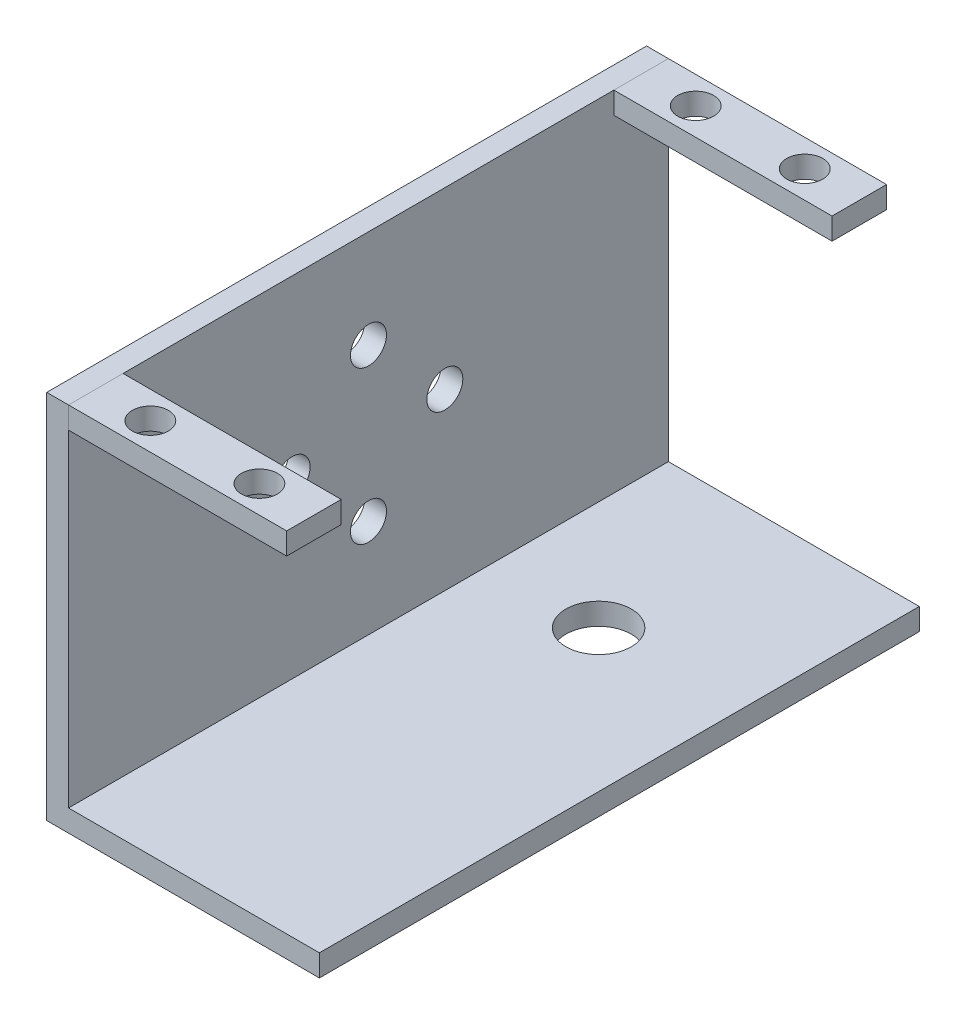
SolidWorks part; units mm, degrees
ref_plane "前视基准面" through (0, 0, 0) normal (0, 0, 1) x (1, 0, 0)
ref_plane "上视基准面" through (0, 0, 0) normal (0, 1, 0) x (1, 0, 0)
ref_plane "右视基准面" through (0, 0, 0) normal (1, 0, 0) x (0, 0, -1)
sketch "草图1" plane through (0, 0, 0) normal (0, 1, 0) x (1, 0, 0)
  line L1 (-12.5, -27.5) -> (12.5, -27.5)
  line L2 (-12.5, -27.5) -> (-12.5, 27.5)
  line L3 (-12.5, 27.5) -> (12.5, 27.5)
  line L4 (12.5, -27.5) -> (12.5, 27.5)
  line L5 (-12.5, -27.5) -> (12.5, 27.5) construction
  line L6 (-12.5, 27.5) -> (12.5, -27.5) construction
  point P1 (0, 0)
  dimension "D1" = 55
  dimension "D2" = 25
extrude "凸台-拉伸1" add sketch "草图1" along normal blind 2
sketch "草图3" plane through (0, 2, 0) normal (0, 1, 0) x (1, 0, 0)
  line L0 (-12.5, -27.5) -> (12.5, -27.5) construction
  line L1 (-12.5, 27.5) -> (-10.5, 27.5)
  line L2 (-12.5, 27.5) -> (-12.5, -27.5)
  line L3 (-12.5, -27.5) -> (-10.5, -27.5)
  line L4 (-10.5, 27.5) -> (-10.5, -27.5)
  dimension "D1" = 2
extrude "凸台-拉伸2" add sketch "草图3" along normal blind 32
sketch "草图4" plane through (-10.5, 0, 0) normal (1, 0, 0) x (0, 0, -1)
  line L0 (0, 34) -> (0, 2) construction
  line L1 (-27.5, 34) -> (27.5, 34) construction
  line L2 (-27.5, 2) -> (27.5, 2) construction
  line L3 (-22.5, 32) -> (22.5, 32) construction
  line L4 (22.5, 34) -> (27.5, 34)
  line L5 (-22.5, 32) -> (-27.5, 32)
  line L6 (-22.5, 32) -> (-22.5, 34)
  line L7 (-22.5, 34) -> (-27.5, 34)
  line L8 (-27.5, 32) -> (-27.5, 34)
  line L9 (27.5, 32) -> (27.5, 34)
  line L10 (22.5, 32) -> (27.5, 32)
  line L11 (22.5, 32) -> (22.5, 34)
  line L12 (-27.5, 2) -> (27.5, 2) construction
  dimension "D1" = 45
  dimension "D2" = 5
  dimension "D3" = 2
  dimension "D4" = 30
extrude "凸台-拉伸3" add sketch "草图4" along normal blind 20 separate body
sketch "草图5" plane through (0, 34, 0) normal (0, 1, 0) x (1, 0, 0)
  line L0 (-10.5, -25) -> (9.5, -25) construction
  line L1 (-10.5, -22.5) -> (-10.5, -27.5) construction
  line L2 (9.5, -22.5) -> (9.5, -27.5) construction
  line L3 (-12.5, 0) -> (-10.5, 0) construction
  line L4 (-12.5, 27.5) -> (-12.5, -27.5) construction
  line L5 (-10.5, -27.5) -> (-10.5, 27.5) construction
  circle A0 centre (-5.5, -25) radius 1.65
  circle A1 centre (4.5, -25) radius 1.65
  circle A2 centre (4.5, 25) radius 1.65
  circle A3 centre (-5.5, 25) radius 1.65
  dimension "D1" = 3.3
  dimension "D2" = 3.3
  dimension "D3" = 10
  dimension "D4" = 5
extrude "切除-拉伸2" cut sketch "草图5" against normal up to next (2 mm away)
sketch "草图6" plane through (-10.5, 0, 0) normal (1, 0, 0) x (0, 0, -1)
  line L0 (-27.5, 18) -> (27.5, 18) construction
  line L1 (-27.5, 34) -> (-27.5, 2) construction
  line L2 (27.5, 34) -> (27.5, 2) construction
  line L3 (0, 34) -> (0, 2) construction
  line L4 (-27.5, 34) -> (27.5, 34) construction
  line L5 (-27.5, 2) -> (27.5, 2) construction
  circle A0 centre (-7, 18) radius 1.65
  circle A1 centre (7, 18) radius 1.65
  circle A2 centre (0, 25) radius 1.65
  circle A3 centre (0, 11) radius 1.65
  point P20 (0, 0)
  point P21 (0, 0)
  point P22 (0, 0)
  dimension "D1" = 3.3
  dimension "D2" = 3.3
  dimension "D3" = 3.3
  dimension "D4" = 3.3
  dimension "D5" = 14
  dimension "D6" = 14
extrude "切除-拉伸3" cut sketch "草图6" against normal blind 10
sketch "草图7" plane through (0, 2, 0) normal (0, 1, 0) x (1, 0, 0)
  line L0 (4.5, 25) -> (-5.5, 25) construction
  line L1 (4.5, 25) -> (4.5, -25) construction
  circle A0 centre (-0.5, 11.1) radius 3
  point P10 (-0.0903, 25)
  dimension "D3" = 6
  dimension "D1" = 5
  dimension "D2" = 13.9
extrude "切除-拉伸4" cut sketch "草图7" against normal blind 10
